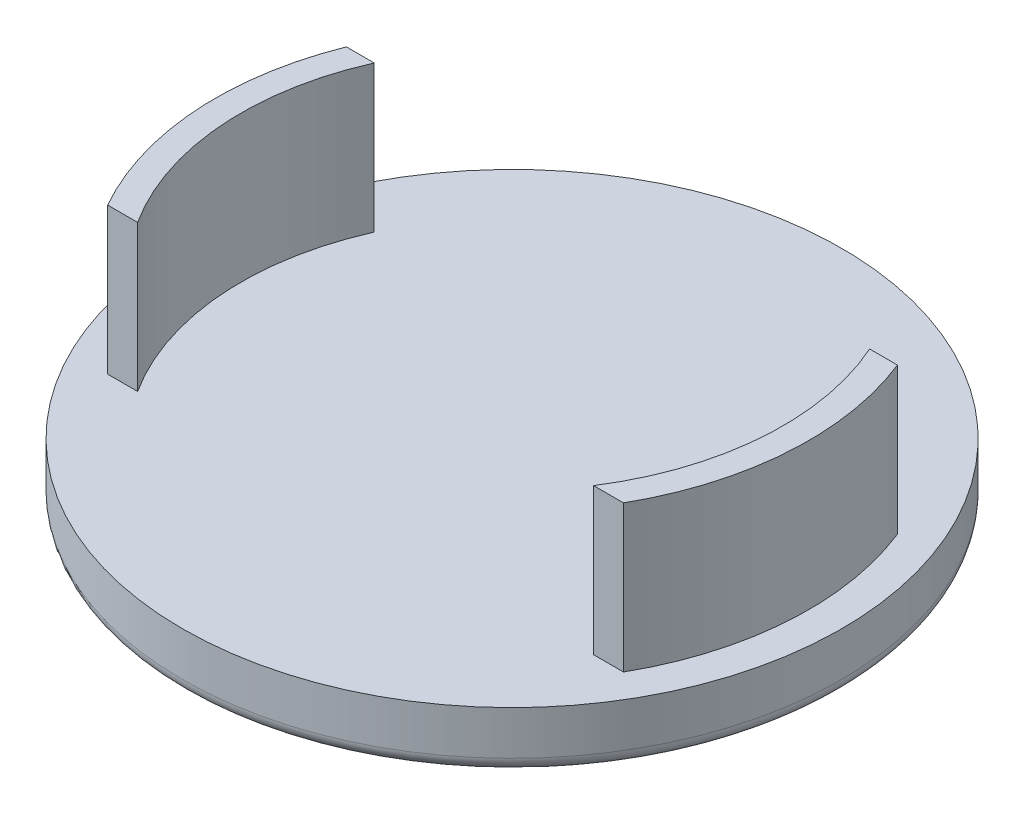
SolidWorks part; units mm, degrees
ref_plane "Front Plane" through (0, 0, 0) normal (0, 0, 1) x (1, 0, 0)
ref_plane "Top Plane" through (0, 0, 0) normal (0, 1, 0) x (1, 0, 0)
ref_plane "Right Plane" through (0, 0, 0) normal (1, 0, 0) x (0, 0, -1)
sketch "Sketch1" plane through (0, 0, 0) normal (0, 1, 0) x (1, 0, 0)
  circle A0 centre (0, 0) radius 22.5
  circle A1 centre (0, 0) radius 20.25
  circle A2 centre (0, 0) radius 18.5
  dimension "D1" = 45
  dimension "D2" = 40.5
  dimension "D3" = 37
extrude "Boss-Extrude1" add sketch "Sketch1" along normal blind 4 contours A0 A1 | A1 A2 | A2 region at (-21.8636, 0, 0) region at (-19.6772, 0, 0) region at (0, 0, 0)
sketch "Sketch2" plane through (0, 4, 0) normal (0, 1, 0) x (1, 0, 0)
  circle A0 centre (0, 0) radius 20.25
  circle A1 centre (0, 0) radius 18.5
  dimension "D1" = 40.5
  dimension "D2" = 37
extrude "Boss-Extrude2" add sketch "Sketch2" along normal blind 10
sketch "Sketch3" plane through (0, 14, 0) normal (0, 1, 0) x (1, 0, 0)
  line L1 (-24.1851, 23.1335) -> (22.3301, 23.1335)
  line L2 (-24.1851, 23.1335) -> (-24.1851, 7.5)
  line L3 (-24.1851, 7.5) -> (22.3301, 7.5)
  line L4 (22.3301, 23.1335) -> (22.3301, 7.5)
  line L5 (-21.2125, -10) -> (19.7979, -10)
  line L6 (-21.2125, -10) -> (-21.2125, -21.6701)
  line L7 (-21.2125, -21.6701) -> (19.7979, -21.6701)
  line L8 (19.7979, -10) -> (19.7979, -21.6701)
  dimension "D1" = 10
  dimension "D2" = 7.5
extrude "Cut-Extrude1" cut sketch "Sketch3" against normal blind 10
fillet "Fillet1" radius 1 1 edges at (0, 0, 22.5)
